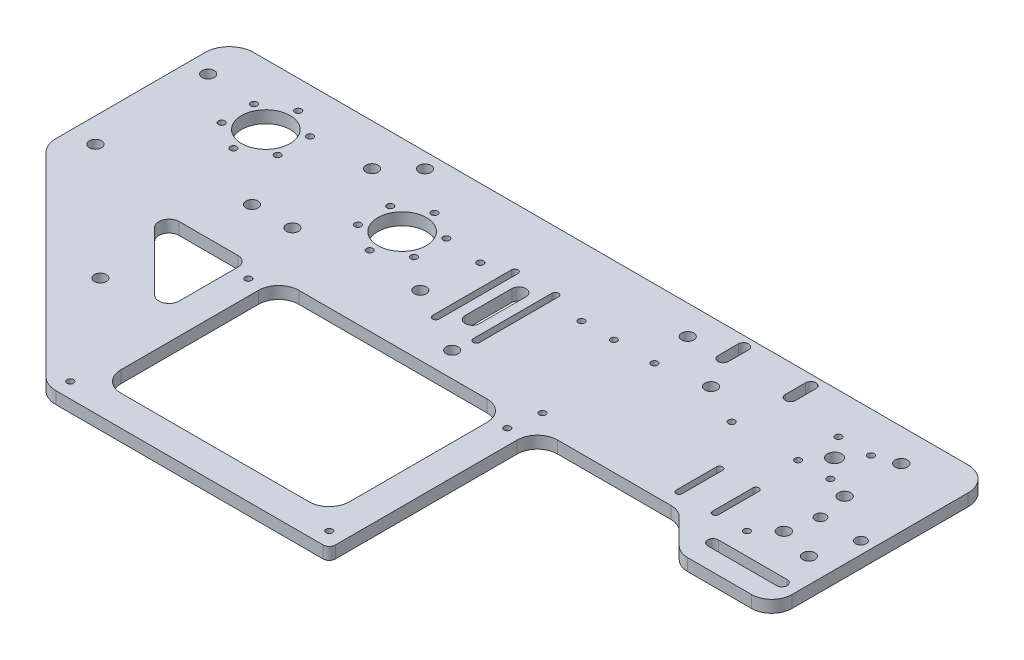
SolidWorks part; units mm, degrees
material "Policarbonato"
ref_plane "Plano frontal" through (0, 0, 0) normal (0, 0, 1) x (1, 0, 0)
ref_plane "Plano superior" through (0, 0, 0) normal (0, 1, 0) x (1, 0, 0)
ref_plane "Plano direito" through (0, 0, 0) normal (1, 0, 0) x (0, 0, -1)
sketch "Esboço1" plane through (0, 0, 0) normal (0, 1, 0) x (1, 0, 0)
  line L3 (-80.5574, -153.6487) -> (51.4721, -153.6487)
  line L4 (54.4721, -150.6487) -> (54.4721, -60.7886)
  line L6 (188.5279, -40.7886) -> (188.5279, 28)
  line L7 (176.5279, 40) -> (-176.5279, 40)
  line L8 (-188.5279, 28) -> (-188.5279, -45.6781)
  line L12 (-122.5768, -50.7886) -> (-93.5279, -50.7886)
  line L13 (-88.5279, -55.7886) -> (-88.5279, -84.8375)
  line L14 (-97.0635, -88.373) -> (-126.1124, -59.3241)
  line L15 (39.4721, -60.6487) -> (39.4721, -128.6487)
  line L16 (29.4721, -138.6487) -> (-63.5279, -138.6487)
  line L17 (-73.5279, -128.6487) -> (-73.5279, -60.6487)
  line L18 (-63.5279, -50.6487) -> (29.4721, -50.6487)
  line L20 (132.5279, 0) -> (148.5279, 0) construction
  line L21 (132.5279, 0) -> (132.5279, 20) construction
  line L22 (132.5279, 20) -> (148.5279, 20) construction
  line L23 (148.5279, 0) -> (148.5279, 20) construction
  line L24 (132.5279, 0) -> (148.5279, 20) construction
  line L25 (132.5279, 20) -> (148.5279, 0) construction
  line L30 (64.4721, -50.7886) -> (178.5279, -50.7886)
  line L31 (134.7221, -43) -> (134.7221, -23) construction
  line L32 (133.2221, -43) -> (133.2221, -23)
  line L33 (136.2221, -43) -> (136.2221, -23)
  line L34 (125.7221, -45.2211) -> (125.7221, -21.4375) construction
  line L36 (116.7221, -43) -> (116.7221, -23) construction
  line L37 (118.2221, -43) -> (118.2221, -23)
  line L38 (115.2221, -43) -> (115.2221, -23)
  line L40 (54.4721, -120.5) -> (144.9721, -120.5) construction
  line L41 (54.4721, -120.5) -> (54.4721, -7) construction
  line L42 (54.4721, -7) -> (144.9721, -7) construction
  line L43 (144.9721, -120.5) -> (144.9721, -7) construction
  line L44 (54.4721, -120.5) -> (144.9721, -7) construction
  line L45 (54.4721, -7) -> (144.9721, -120.5) construction
  line L46 (70.5279, 25) -> (70.5279, 35) construction
  line L47 (67.9779, 25) -> (67.9779, 35)
  line L48 (73.0779, 25) -> (73.0779, 35)
  line L49 (103.7779, 25) -> (103.7779, 35) construction
  line L50 (101.2279, 25) -> (101.2279, 35)
  line L51 (106.3279, 25) -> (106.3279, 35)
  line L52 (-185.0132, -54.1634) -> (-89.0426, -150.134)
  circle A0 centre (-81.0279, -58.1487) radius 1.6
  circle A1 centre (-81.0279, -146.1487) radius 1.6
  circle A2 centre (46.9721, -58.1487) radius 1.6
  circle A3 centre (46.9721, -146.1487) radius 1.6
  circle A8 centre (176.311, -38.4318) radius 3
  circle A9 centre (0, -38.4318) radius 3
  circle A11 centre (-140.5279, 10) radius 12
  circle A20 centre (-140.5279, 10) radius 16 construction
  circle A21 centre (-140.5279, -6) radius 1.6
  circle A22 centre (-154.3843, 2) radius 1.6
  circle A23 centre (-154.3843, 18) radius 1.6
  circle A24 centre (-84.3674, 32.5) radius 3
  circle A25 centre (-176.311, -38.4318) radius 3
  circle A26 centre (140.5279, 10) radius 3.5
  circle A27 centre (148.5279, 0) radius 1.6
  circle A28 centre (148.5279, 20) radius 1.6
  circle A29 centre (132.5279, 0) radius 1.6
  circle A30 centre (132.5279, 20) radius 1.6
  arc A31 (51.4721, -153.6487) -> (54.4721, -150.6487) centre (51.4721, -150.6487) ccw
  arc A34 (188.5279, 28) -> (176.5279, 40) centre (176.5279, 28) ccw
  arc A35 (-176.5279, 40) -> (-188.5279, 28) centre (-176.5279, 28) ccw
  arc A39 (-93.5279, -50.7886) -> (-88.5279, -55.7886) centre (-93.5279, -55.7886) cw
  arc A40 (-88.5279, -84.8375) -> (-97.0635, -88.373) centre (-93.5279, -84.8375) cw
  arc A41 (-126.1124, -59.3241) -> (-122.5768, -50.7886) centre (-122.5768, -55.7886) cw
  arc A42 (39.4721, -128.6487) -> (29.4721, -138.6487) centre (29.4721, -128.6487) cw
  arc A43 (-63.5279, -138.6487) -> (-73.5279, -128.6487) centre (-63.5279, -128.6487) cw
  arc A44 (-73.5279, -60.6487) -> (-63.5279, -50.6487) centre (-63.5279, -60.6487) cw
  arc A45 (29.4721, -50.6487) -> (39.4721, -60.6487) centre (29.4721, -60.6487) cw
  circle A46 centre (-140.5279, 26) radius 1.6
  circle A47 centre (-126.6715, 18) radius 1.6
  circle A48 centre (-126.6715, 2) radius 1.6
  circle A49 centre (-63.1716, 0) radius 16 construction
  circle A50 centre (-63.1716, -16) radius 1.6
  circle A51 centre (-77.028, -8) radius 1.6
  circle A52 centre (-77.028, 8) radius 1.6
  circle A53 centre (-63.1716, 16) radius 1.6
  circle A54 centre (-49.3152, 8) radius 1.6
  circle A55 centre (-49.3152, -8) radius 1.6
  circle A56 centre (-63.1716, 0) radius 12
  circle A57 centre (-33.5279, -20.6487) radius 3
  circle A58 centre (79.5279, 10) radius 3
  arc A62 (188.5279, -40.7886) -> (178.5279, -50.7886) centre (178.5279, -40.7886) cw
  arc A63 (54.4721, -60.7886) -> (64.4721, -50.7886) centre (64.4721, -60.7886) cw
  arc A64 (133.2221, -43) -> (136.2221, -43) centre (134.7221, -43) ccw
  arc A65 (136.2221, -23) -> (133.2221, -23) centre (134.7221, -23) ccw
  arc A66 (118.2221, -43) -> (115.2221, -43) centre (116.7221, -43) cw
  arc A67 (115.2221, -23) -> (118.2221, -23) centre (116.7221, -23) cw
  circle A68 centre (99.7221, 0) radius 1.6
  circle A69 centre (49.2221, -43) radius 1.6
  circle A70 centre (134.7221, -43) radius 1.6 construction
  circle A71 centre (-30.5279, 6) radius 1.6
  circle A72 centre (19.4721, 6) radius 1.6
  circle A73 centre (55.5279, 6) radius 1.6
  circle A75 centre (35.5279, 6) radius 1.6
  circle A76 centre (70.5279, 30) radius 2.55 construction
  circle A77 centre (103.7779, 30) radius 2.55 construction
  circle A78 centre (159.4679, 24.07) radius 3.05
  circle A79 centre (159.4679, -3.93) radius 3.05
  circle A80 centre (159.4679, -33.93) radius 3.05
  arc A81 (67.9779, 25) -> (73.0779, 25) centre (70.5279, 25) ccw
  arc A82 (73.0779, 35) -> (67.9779, 35) centre (70.5279, 35) ccw
  arc A83 (101.2279, 25) -> (106.3279, 25) centre (103.7779, 25) ccw
  arc A84 (106.3279, 35) -> (101.2279, 35) centre (103.7779, 35) ccw
  circle A85 centre (-178.5279, 19.5) radius 3
  circle A86 centre (-97.5279, 19.5) radius 3
  arc A87 (-80.5574, -153.6487) -> (-89.0426, -150.134) centre (-80.5574, -141.6487) cw
  arc A88 (-185.0132, -54.1634) -> (-188.5279, -45.6781) centre (-176.5279, -45.6781) cw
  circle A89 centre (52.3279, 25.68) radius 3
  circle A90 centre (150.2221, -43) radius 1.6
  point P14 (134.7221, -33)
  point P43 (-140.5279, 10)
  point P70 (-144.4721, -50.6487)
  point P82 (-85.5279, -153.6487)
  point P116 (-63.1716, 0)
  point P123 (0, 40)
  point P124 (116.7221, -33)
  point P129 (99.7221, -63.75)
  point P141 (99.7221, -7)
  point P161 (70.5279, 30)
  point P168 (103.7779, 30)
  dimension "D2" = 3
  dimension "D8" = 12
  dimension "D10" = 12
  dimension "D11" = 61
  dimension "D12" = 203.9448
  dimension "D13" = 7.5
  dimension "D14" = 104.1605
  dimension "D16" = 135.7229
  dimension "D20" = 19.68
  dimension "D21" = 3.2
  dimension "D22" = 48.4318
  dimension "D23" = 32
  dimension "D24" = 3.2
  dimension "D25" = 6
  dimension "D26" = 24
  dimension "D27" = 48
  dimension "D28" = 30
  dimension "D29" = 40
  dimension "D30" = 6
  dimension "D34" = 30
  dimension "D31" = 32
  dimension "D32" = 3.2
  dimension "D33" = 24
  dimension "D35" = 6
  dimension "D36" = 155
  dimension "D37" = 30
  dimension "D44" = 7
  dimension "D48" = 10
  dimension "D54" = 50.5
  dimension "D6" = 10
  dimension "D58" = 5
  dimension "D62" = 1.5
  dimension "D72" = 85
  dimension "D75" = 5.1
  dimension "D80" = 14.07
  dimension "D82" = 6.1
  dimension "D83" = 10
  dimension "D19" = 6
  dimension "D47" = 101
  dimension "D1" = 137
  dimension "D9" = 377.0558
  dimension "D15" = 225
  dimension "D17" = 38
  dimension "D18" = 15
  dimension "D38" = 48
  dimension "D39" = 15
  dimension "D40" = 12.2169
  dimension "D41" = 12.2169
  dimension "D42" = 16
  dimension "D43" = 20
  dimension "D45" = 15
  dimension "D46" = 15
  dimension "D49" = 7.5
  dimension "D50" = 7.5
  dimension "D51" = 88
  dimension "D52" = 128
  dimension "D53" = 93
  dimension "D56" = 20.6487
  dimension "D57" = 68
  dimension "D59" = 10
  dimension "D60" = 20.5
  dimension "D61" = 20
  dimension "D63" = 9
  dimension "D64" = 113.5
  dimension "D65" = 90.5
  dimension "D66" = 7
  dimension "D67" = 43
  dimension "D69" = 34
  dimension "D70" = 110
  dimension "D71" = 50
  dimension "D73" = 20
  dimension "D74" = 33.25
  dimension "D76" = 10
  dimension "D77" = 15
  dimension "D78" = 30
  dimension "D79" = 28
  dimension "D81" = 18.94
  dimension "D84" = 81
extrude "Ressalto-extrusão1" add sketch "Esboço1" against normal blind 6
sketch "Esboço2" plane through (0, 0, 0) normal (0, 1, 0) x (1, 0, 0)
  line L0 (188.5279, -40.7886) -> (188.5279, 28) construction
  line L1 (-126.1124, -59.3241) -> (-97.0635, -88.373) construction
  line L2 (-131.2731, -107.9035) -> (-104.403, -81.0335) construction
  line L3 (-185.0132, -54.1634) -> (-89.0426, -150.134) construction
  line L4 (159.4679, -6.98) -> (159.4679, -30.88) construction
  line L5 (-140.5279, 10) -> (-63.1716, 0) construction
  line L6 (176.5279, 40) -> (-176.5279, 40) construction
  line L7 (-91.8498, -25.5) -> (-111.8498, -25.5) construction
  circle A1 centre (-117.8381, -94.4685) radius 3
  arc A2 (-188.5279, -45.6781) -> (-185.0132, -54.1634) centre (-176.5279, -45.6781) ccw construction
  circle A3 centre (182.5279, -18.93) radius 2.6
  circle A4 centre (162.5279, -18.93) radius 2.6
  circle A7 centre (-111.8498, -25.5) radius 3
  circle A8 centre (-91.8498, -25.5) radius 3
  circle A9 centre (159.4679, -3.93) radius 3.05 construction
  circle A10 centre (159.4679, -33.93) radius 3.05 construction
  point P1 (-117.8381, -94.4685)
  point P18 (159.4679, -18.93)
  point P30 (-101.8498, 5)
  point P41 (-101.8498, -25.5)
  dimension "D1" = 76
  dimension "D2" = 6
  dimension "D3" = 20
  dimension "D4" = 5.2
  dimension "D5" = 6
  dimension "D6" = 6
  dimension "D7" = 65.5
  dimension "D8" = 20
extrude "Corte-extrusão1" cut sketch "Esboço2" against normal blind 10
sketch "Esboço3" plane through (0, 0, 0) normal (0, 1, 0) x (1, 0, 0)
  line L0 (142.7858, -68.9886) -> (114.5858, -40.7886)
  line L1 (188.5279, -40.7886) -> (142.7858, -40.7886)
  line L2 (188.5279, -40.7886) -> (188.5279, -68.9886)
  line L3 (188.5279, -68.9886) -> (142.7858, -68.9886)
  line L4 (142.7858, -40.7886) -> (142.7858, -68.9886)
  line L5 (114.5858, -40.7886) -> (142.7858, -40.7886)
  line L6 (180.9279, -56.3886) -> (146.9279, -56.3886) construction
  line L7 (180.9279, -58.9886) -> (146.9279, -58.9886)
  line L8 (180.9279, -53.7886) -> (146.9279, -53.7886)
  line L10 (133.2221, -23) -> (133.2221, -43) construction
  line L11 (136.2221, -43) -> (136.2221, -23) construction
  line L12 (133.2221, -23) -> (133.2221, -43)
  line L13 (136.2221, -43) -> (136.2221, -23)
  line L14 (115.2221, -23) -> (115.2221, -43) construction
  line L15 (118.2221, -43) -> (118.2221, -23) construction
  line L16 (115.2221, -23) -> (115.2221, -43)
  line L17 (118.2221, -43) -> (118.2221, -23)
  line L18 (64.4721, -50.7886) -> (178.5279, -50.7886) construction
  arc A0 (180.9279, -58.9886) -> (180.9279, -53.7886) centre (180.9279, -56.3886) ccw
  arc A1 (146.9279, -53.7886) -> (146.9279, -58.9886) centre (146.9279, -56.3886) ccw
  circle A2 centre (176.311, -38.4318) radius 3 construction
  arc A3 (133.2221, -43) -> (136.2221, -43) centre (134.7221, -43) ccw construction
  circle A4 centre (176.311, -38.4318) radius 3
  arc A5 (133.2221, -43) -> (136.2221, -43) centre (134.7221, -43) ccw
  arc A6 (115.2221, -43) -> (118.2221, -43) centre (116.7221, -43) ccw construction
  arc A7 (115.2221, -43) -> (118.2221, -43) centre (116.7221, -43) ccw
  circle A8 centre (150.2221, -43) radius 1.6 construction
  circle A9 centre (150.2221, -43) radius 1.6
  point P8 (163.9279, -56.3886)
  point P13 (183.5279, -56.3886)
  point P16 (144.3279, -56.3886)
  dimension "D3" = 2.6
  dimension "D1" = 45
  dimension "D2" = 34
  dimension "D4" = 10
  dimension "D5" = 10
  dimension "D6" = 5
  dimension "D7" = 3
extrude "Ressalto-extrusão2" add sketch "Esboço3" against normal up to surface (6 mm away) contours L5 L0 L4 | L1 L4 L3 L2 A1 L8 A0 L7 region at (143.3231, 0, 54.8886) region at (133.6258, 0, 50.5324) up to face at (-117.8381, -6, 91.4685)
fillet "Filete1" radius 10 3 edges at (188.5279, -3, 68.9886) (142.7858, -3, 68.9886) (124.5858, -3, 50.7886)
sketch "Esboço4" plane through (0, 0, 0) normal (0, 1, 0) x (1, 0, 0)
  line L0 (-63.1716, 0) -> (140.5279, 10) construction
  line L1 (-8.1716, 2.7001) -> (-8.1716, -20.2999) construction
  line L2 (-4.6716, 2.7001) -> (-4.6716, -20.2999)
  line L3 (-11.6716, 2.7001) -> (-11.6716, -20.2999)
  line L4 (1.8284, 10.7001) -> (1.8284, -12.2999) construction
  line L5 (3.4284, 10.7001) -> (3.4284, -12.2999)
  line L6 (0.2284, 10.7001) -> (0.2284, -12.2999)
  line L7 (1.8284, -5.2999) -> (1.8284, -28.2999) construction
  line L8 (3.4284, -5.2999) -> (3.4284, -28.2999)
  line L9 (0.2284, -5.2999) -> (0.2284, -28.2999)
  line L10 (-8.1716, 2.7001) -> (-8.1716, 10.7001) construction
  line L11 (-18.1716, -5.2999) -> (-18.1716, -28.2999) construction
  line L12 (-19.7716, -5.2999) -> (-19.7716, -28.2999)
  line L13 (-16.5716, -5.2999) -> (-16.5716, -28.2999)
  line L14 (-18.1716, 10.7001) -> (-18.1716, -12.2999) construction
  line L15 (-19.7716, 10.7001) -> (-19.7716, -12.2999)
  line L16 (-16.5716, 10.7001) -> (-16.5716, -12.2999)
  arc A0 (-4.6716, 2.7001) -> (-11.6716, 2.7001) centre (-8.1716, 2.7001) ccw
  arc A1 (-11.6716, -20.2999) -> (-4.6716, -20.2999) centre (-8.1716, -20.2999) ccw
  arc A2 (3.4284, 10.7001) -> (0.2284, 10.7001) centre (1.8284, 10.7001) ccw
  arc A3 (0.2284, -12.2999) -> (3.4284, -12.2999) centre (1.8284, -12.2999) ccw
  arc A4 (3.4284, -5.2999) -> (0.2284, -5.2999) centre (1.8284, -5.2999) ccw
  arc A5 (0.2284, -28.2999) -> (3.4284, -28.2999) centre (1.8284, -28.2999) ccw
  circle A6 centre (-63.1716, 16) radius 1.6 construction
  arc A7 (-19.7716, -5.2999) -> (-16.5716, -5.2999) centre (-18.1716, -5.2999) cw
  arc A8 (-16.5716, -28.2999) -> (-19.7716, -28.2999) centre (-18.1716, -28.2999) cw
  arc A9 (-19.7716, 10.7001) -> (-16.5716, 10.7001) centre (-18.1716, 10.7001) cw
  arc A10 (-16.5716, -12.2999) -> (-19.7716, -12.2999) centre (-18.1716, -12.2999) cw
  circle A11 centre (140.5279, 10) radius 3.5 construction
  point P6 (-8.1716, -8.7999)
  point P11 (1.8284, -0.7999)
  point P18 (1.8284, -16.7999)
  point P31 (-18.1716, -16.7999)
  point P38 (-18.1716, -0.7999)
  dimension "D1" = 16
  dimension "D2" = 23
  dimension "D3" = 20
  dimension "D4" = 8
  dimension "D5" = 55
extrude "Corte-extrusão2" cut sketch "Esboço4" against normal through all contours L6 A3 L5 A2 | L9 A5 L8 A4 | L3 A1 L2 A0 | L12 A8 L13 A7 | L15 A10 L16 A9
